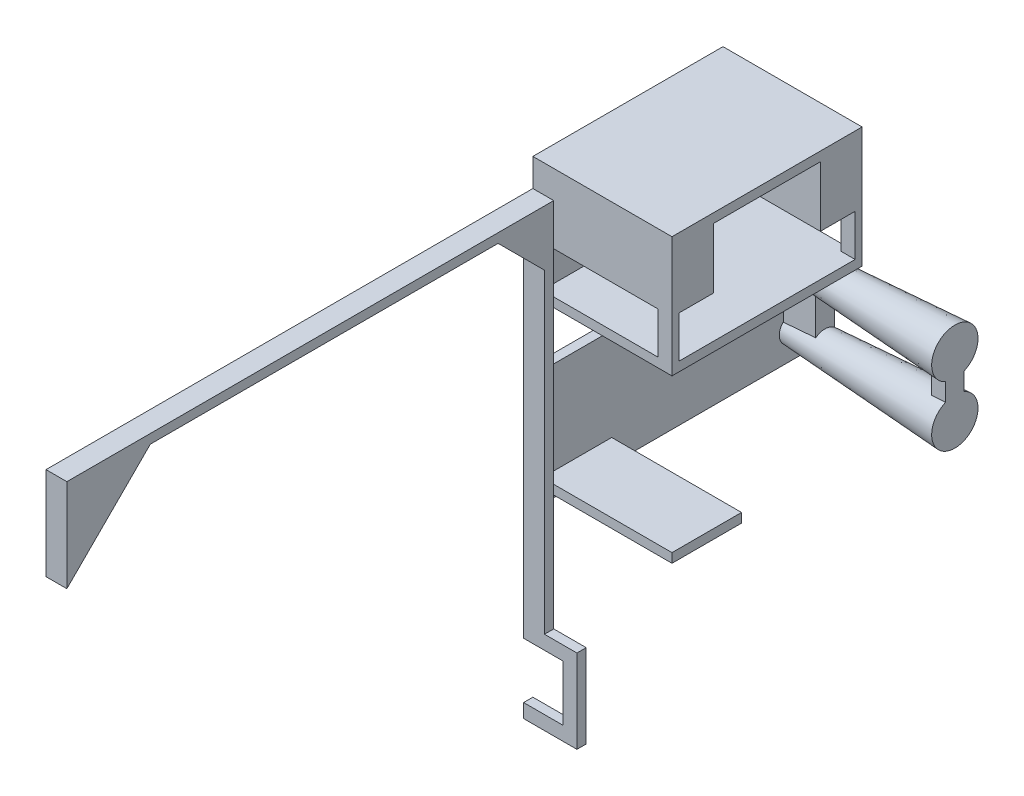
SolidWorks part; units mm, degrees
ref_plane "Front Plane" through (0, 0, 0) normal (0, 0, 1) x (1, 0, 0)
ref_plane "Top Plane" through (0, 0, 0) normal (0, 1, 0) x (1, 0, 0)
ref_plane "Right Plane" through (0, 0, 0) normal (1, 0, 0) x (0, 0, -1)
sketch "Sketch6" plane through (0, 0, 0) normal (1, 0, 0) x (0, 0, -1)
  line L1 (0, 0) -> (105, 0)
  line L2 (0, 0) -> (0, -83)
  line L3 (0, -83) -> (105, -83)
  line L4 (105, 0) -> (105, -83)
  dimension "D1" = 105
  dimension "D2" = 83
extrude "Boss-Extrude3" add sketch "Sketch6" along normal blind 4.5
sketch "Sketch9" plane through (0, -83, 0) normal (0, -1, 0) x (1, 0, 0)
  line L0 (4.5, 0) -> (4.5, -105) construction
  line L1 (0, 0) -> (0, -105) construction
  line L2 (4.5, -2) -> (1.5, -2)
  line L3 (4.5, -2) -> (4.5, -103)
  line L4 (4.5, -103) -> (1.5, -103)
  line L5 (1.5, -2) -> (1.5, -103)
  line L6 (4.5, 0) -> (0, 0) construction
  line L7 (4.5, -105) -> (0, -105) construction
  dimension "D1" = 1.5
  dimension "D2" = 2
  dimension "D3" = 2
extrude "Cut-Extrude6" cut sketch "Sketch9" against normal blind 81
sketch "Sketch10" plane through (0, 0, -2) normal (0, 0, -1) x (-1, 0, 0)
  line L1 (-4.5, -2) -> (-3.5, -2)
  line L2 (-4.5, -2) -> (-4.5, -10)
  line L3 (-4.5, -10) -> (-3.5, -10)
  line L4 (-3.5, -2) -> (-3.5, -10)
  dimension "D1" = 1
  dimension "D2" = 8
extrude "Boss-Extrude4" add sketch "Sketch10" along normal blind 8
sketch "Sketch11" plane through (0, 0, -103) normal (0, 0, 1) x (1, 0, 0)
  line L1 (4.5, -2) -> (3.2738, -2)
  line L2 (4.5, -2) -> (4.5, -7)
  line L3 (4.5, -7) -> (3.2738, -7)
  line L4 (3.2738, -2) -> (3.2738, -7)
  dimension "D1" = 5
extrude "Boss-Extrude5" add sketch "Sketch11" along normal blind 5
sketch "Sketch18" plane through (4.5, 0, 0) normal (1, 0, 0) x (0, 0, -1)
  line L0 (103, -12) -> (93, -2)
  line L1 (103, -7) -> (103, -83) construction
  line L2 (98, -2) -> (10, -2) construction
  line L3 (103, -12) -> (103, -2)
  line L4 (103, -2) -> (93, -2)
  line L5 (18, -2) -> (2, -2)
  line L6 (2, -2) -> (2, -18)
  line L7 (2, -10) -> (2, -83) construction
  line L8 (2, -18) -> (18, -2)
  dimension "D1" = 0
  dimension "D2" = 10
  dimension "D3" = 0
  dimension "D4" = 16
  dimension "D5" = 22.6274
extrude "Boss-Extrude12" add sketch "Sketch18" against normal up to vertex (1.2262 mm away) up to point (3.2738, -7, -98)
sketch "Sketch27" plane through (0, 0, 0) normal (-1, 0, 0) x (0, 0, 1)
  line L0 (-105, -83) -> (-105, 0) construction
  line L1 (-105, -55) -> (-120, -55)
  line L2 (-105, -55) -> (-105, -53)
  line L3 (-105, -53) -> (-120, -53)
  line L4 (-120, -55) -> (-120, -53)
  line L5 (-125.5, -18) -> (-125.5, 21.7068) construction
  line L6 (-105, -20) -> (-146, -20)
  line L7 (-105, -20) -> (-105, -18)
  line L8 (-105, -18) -> (-146, -18)
  line L9 (-146, -20) -> (-146, -18)
  line L10 (-105, -9) -> (-114, -9)
  line L11 (-105, -9) -> (-105, 6)
  line L12 (-105, 6) -> (-114, 6)
  line L13 (-114, -9) -> (-114, 6)
  line L14 (-146, 6) -> (-137, 6)
  line L15 (-137, -9) -> (-137, 6)
  line L16 (-146, -9) -> (-137, -9)
  line L17 (-146, -9) -> (-146, 6)
  dimension "D1" = 15
  dimension "D2" = 28
  dimension "D3" = 63
  dimension "D4" = 41
  dimension "D5" = 2
  dimension "D6" = 2
  dimension "D7" = 9
  dimension "D8" = 15
  dimension "D9" = 9
extrude "Boss-Extrude20" add sketch "Sketch27" against normal blind 30
sketch "Sketch28" plane through (30, 0, 0) normal (1, 0, 0) x (0, 0, -1)
  line L0 (146, -9) -> (137, -9) construction
  line L1 (146, -20) -> (144.5, -20)
  line L2 (146, -20) -> (146, -9)
  line L3 (146, -9) -> (144.5, -9)
  line L4 (144.5, -20) -> (144.5, -9)
  line L5 (125.5, -18) -> (125.5, -4.7212) construction
  line L6 (105, -18) -> (146, -18) construction
  line L7 (105, -9) -> (106.5, -9)
  line L8 (106.5, -20) -> (106.5, -9)
  line L9 (105, -20) -> (106.5, -20)
  line L10 (105, -20) -> (105, -9)
  dimension "D1" = 1.5
extrude "Boss-Extrude21" add sketch "Sketch28" against normal blind 3
sketch "Sketch29" plane through (30, 0, 0) normal (1, 0, 0) x (0, 0, -1)
  line L0 (105, -20) -> (105, 6) construction
  line L1 (146, 6) -> (105, 6)
  line L2 (146, 6) -> (146, 4)
  line L3 (146, 4) -> (105, 4)
  line L4 (105, 6) -> (105, 4)
  dimension "D1" = 2
extrude "Boss-Extrude22" add sketch "Sketch29" against normal up to vertex (30 mm away) up to point (0, 6, -105)
sketch "Sketch30" plane through (0, 0, -105) normal (0, 0, -1) x (-1, 0, 0)
  line L0 (0, -83) -> (0, -55) construction
  line L1 (0, -58) -> (-2, -58)
  line L2 (0, -58) -> (0, -33)
  line L3 (0, -33) -> (-2, -33)
  line L4 (-2, -58) -> (-2, -33)
  dimension "D1" = 2
  dimension "D2" = 25
  dimension "D3" = 25
extrude "Boss-Extrude23" add sketch "Sketch30" along normal blind 60
sketch "Sketch31" plane through (2, 0, 0) normal (1, 0, 0) x (0, 0, -1)
  line L0 (165, -58) -> (105, -58) construction
  line L1 (165, -33) -> (165, -58) construction
  line L2 (165, -45.5) -> (129.1416, -45.5) construction
  circle A0 centre (159, -52) radius 5
  circle A1 centre (159, -39) radius 5
  dimension "D1" = 10
  dimension "D2" = 6
  dimension "D3" = 6
extrude "Boss-Extrude24" add sketch "Sketch31" along normal blind 35
draft "Draft1" type of draft neutral plane draft angle 3.5 faces to draft 1 face at (37, -52, -164) neutral plane through (37, -52, -159) neutral plane normal (1, 0, 0) reverse direction yes parameters "D1"=3.5
draft "Draft3" type of draft neutral plane draft angle 3.5 faces to draft 1 face at (37, -39, -154) neutral plane through (37, -39, -159) neutral plane normal (1, 0, 0) reverse direction yes parameters "D1"=3.5
sketch "Sketch32" plane through (2, 0, 0) normal (1, 0, 0) x (0, 0, -1)
  line L1 (161, -53) -> (157, -53)
  line L2 (161, -53) -> (161, -38)
  line L3 (161, -38) -> (157, -38)
  line L4 (157, -53) -> (157, -38)
  circle A0 centre (159, -52) radius 2.8593 construction
  circle A1 centre (159, -39) radius 2.8593 construction
  dimension "D1" = 2
  dimension "D2" = 2
  dimension "D3" = 1
  dimension "D4" = 1
  dimension "D5" = 2
extrude "Boss-Extrude25" add sketch "Sketch32" along normal blind 7
sketch "Sketch33" plane through (37, 0, 0) normal (1, 0, 0) x (0, 0, -1)
  line L1 (157, -39) -> (161, -39)
  line L2 (157, -39) -> (157, -52)
  line L3 (157, -52) -> (161, -52)
  line L4 (161, -39) -> (161, -52)
  circle A0 centre (159, -39) radius 5 construction
  circle A1 centre (159, -52) radius 5 construction
  point P6 (159, -39)
  dimension "D1" = 0
  dimension "D2" = 4
  dimension "D3" = 0
  dimension "D4" = 0
extrude "Boss-Extrude26" add sketch "Sketch33" against normal blind 3
sketch "Sketch34" plane through (4.5, 0, 0) normal (1, 0, 0) x (0, 0, -1)
  line L0 (105, -83) -> (105, -55) construction
  line L1 (103, -83) -> (105, -83)
  line L2 (103, -83) -> (103, -80)
  line L3 (103, -80) -> (105, -80)
  line L4 (105, -83) -> (105, -80)
  dimension "D1" = 3
extrude "Boss-Extrude27" add sketch "Sketch34" along normal blind 4
sketch "Sketch35" plane through (8.5, 0, 0) normal (1, 0, 0) x (0, 0, -1)
  line L0 (105, -83) -> (105, -80) construction
  line L1 (103, -80) -> (105, -80)
  line L2 (103, -80) -> (103, -95)
  line L3 (103, -95) -> (105, -95)
  line L4 (105, -80) -> (105, -95)
  dimension "D1" = 0
  dimension "D2" = 15
extrude "Boss-Extrude28" add sketch "Sketch35" along normal blind 3
sketch "Sketch36" plane through (0, -95, 0) normal (0, -1, 0) x (-1, 0, 0)
  line L0 (0, 0) -> (0, 105) construction
  line L1 (-11.5, 103) -> (0, 103)
  line L2 (-11.5, 103) -> (-11.5, 105)
  line L3 (-11.5, 105) -> (0, 105)
  line L4 (0, 103) -> (0, 105)
  dimension "D1" = 0
extrude "Boss-Extrude29" add sketch "Sketch36" along normal blind 3
sketch "Sketch38" plane through (4.5, 0, 0) normal (1, 0, 0) x (0, 0, -1)
  line L0 (18, -2) -> (0, -20)
  line L1 (0, 0) -> (0, -83) construction
  line L2 (0, -20) -> (0, -83)
  line L3 (0, -83) -> (103, -83)
  line L4 (103, -83) -> (103, -12)
  line L5 (103, -12) -> (93, -2)
  line L6 (93, -2) -> (18, -2)
extrude "Cut-Extrude8" cut sketch "Sketch38" against normal blind 13
sketch "Sketch39" plane through (0, 0, 0) normal (-1, 0, 0) x (0, 0, 1)
  line L1 (-146, 6) -> (-105, 6)
  line L2 (-146, 6) -> (-146, -20)
  line L3 (-146, -20) -> (-105, -20)
  line L4 (-105, 6) -> (-105, -20)
extrude "Boss-Extrude30" add sketch "Sketch39" against normal blind 2
sketch "Sketch40" plane through (2, 0, 0) normal (1, 0, 0) x (0, 0, -1)
  line L1 (114, 4) -> (137, 4) construction
  line L2 (114, -9) -> (114, 4) construction
  circle A0 centre (125.5, -6.5) radius 5
  point P4 (125.5, 4)
  point P7 (114, -2.5)
  dimension "D1" = 0
  dimension "D2" = 4
  dimension "D3" = 10
extrude "Cut-Extrude9" cut sketch "Sketch40" against normal blind 2
